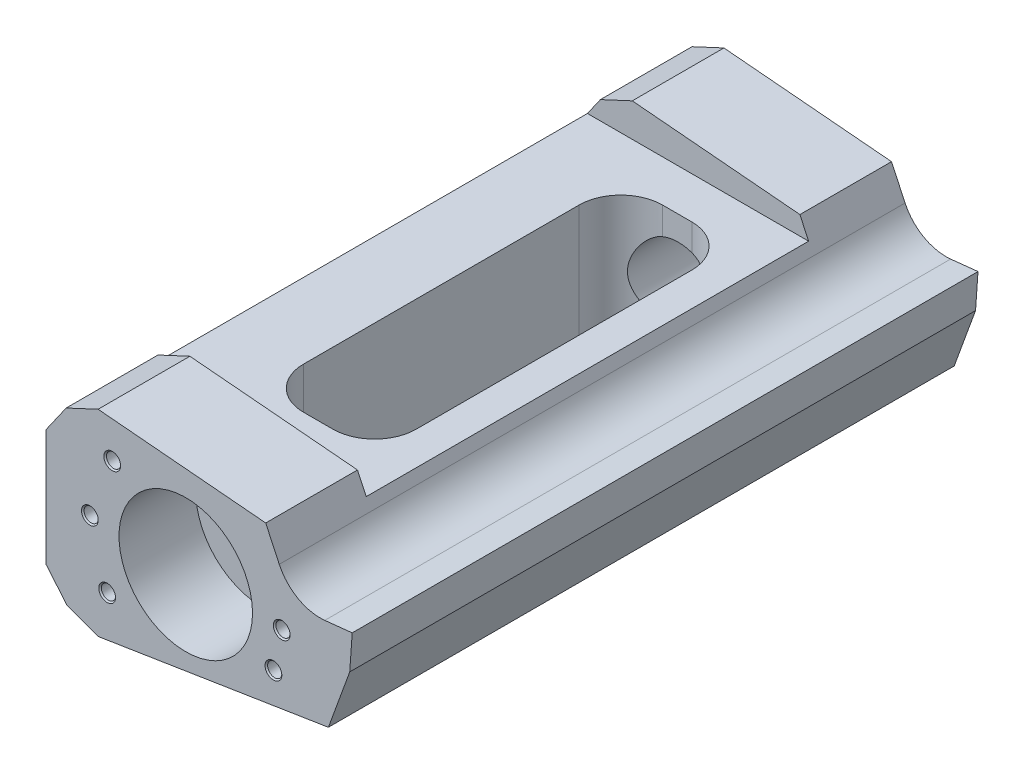
SolidWorks part; units mm, degrees
note: The reader was unsure of these and kept them because the rebuilt part matched: shared geometry of "Esboço7<3>".
material "AISI 4340 Aço, normalizado"
ref_plane "Plano frontal" through (0, 0, 0) normal (0, 0, 1) x (1, 0, 0)
ref_plane "Plano superior" through (0, 0, 0) normal (0, 1, 0) x (1, 0, 0)
ref_plane "Plano direito" through (0, 0, 0) normal (1, 0, 0) x (0, 0, -1)
other "Centro da massa"
sketch "Esboço1" plane through (0, 0, 0) normal (0, 0, 1) x (1, 0, 0)
  line L0 (0, 0) -> (23.1081, 0) construction
  line L1 (64.3164, 0) -> (63.3374, -14)
  line L2 (0, 0) -> (0, 38.7297) construction
  line L3 (-58, -37.4286) -> (54.8101, -37.4286)
  line L39 (29.7708, 20.7479) -> (-37.1899, 26.6062)
  line L40 (-37.1899, 26.6062) -> (-49.9344, 20.6633)
  line L41 (-49.9344, 20.6633) -> (-58, 9.1445)
  line L42 (-58, 9.1445) -> (-58, -37.4286)
  line L43 (-58, -37.4286) -> (-49.5472, -47.5023)
  line L44 (-49.5472, -47.5023) -> (-37.1899, -52)
  line L45 (-37.1899, -52) -> (54.8101, -37.4286)
  line L47 (54.8101, -37.4286) -> (63.3374, -14)
  line L49 (64.3164, 0) -> (53.3766, -1.1498)
  line L50 (35.1816, 9.1445) -> (29.7708, 20.7479)
  arc A0 (53.3766, -1.1498) -> (35.1816, 9.1445) centre (51.4951, 16.7516) cw
  dimension "D2" = 18
  dimension "D1" = 6
  dimension "D3" = 150
  dimension "D4" = 4
  dimension "D5" = 20
  dimension "D6" = 14
  dimension "D7" = 9
  dimension "D8" = 52
  dimension "D9" = 140
  dimension "D10" = 150
  dimension "D11" = 92
  dimension "D12" = 58
  dimension "D13" = 145
  dimension "D14" = 150
  dimension "D16" = 11
  dimension "D17" = 25
extrude "Ressalto-extrusão1" add sketch "Esboço1" along normal blind 250 contours L40 L41 L42 L43 L44 L45 L47 L1 L49 A0 L50 L39
scale "Escala1" scale about centroid uniform scaling yes scale factor 1.5
sketch "Esboço4" plane through (0, 0, -62.5) normal (0, 0, -1) x (-1, 0, 0)
  line L1 (-51.9784, 26.2892) -> (80.5703, 26.2892)
  line L3 (72.8079, 37.3749) -> (80.5703, 26.2892)
  line L4 (72.2271, -64.8736) -> (53.6913, -71.6201) construction
  line L5 (53.6913, -71.6201) -> (-84.3087, -49.763) construction
  line L9 (72.2271, -64.8736) -> (53.6913, -71.6201)
  line L10 (53.6913, -71.6201) -> (-84.3087, -49.763)
  line L11 (53.6913, 46.2892) -> (-46.7499, 37.5017)
  line L12 (-46.7499, 37.5017) -> (-54.866, 20.0966)
  line L13 (-82.1586, 4.6552) -> (-98.5682, 6.3799)
  line L14 (-98.5682, 6.3799) -> (-97.0997, -14.6201)
  line L15 (-97.0997, -14.6201) -> (-84.3087, -49.763)
  line L16 (-84.3087, -49.763) -> (53.6913, -71.6201)
  line L17 (53.6913, -71.6201) -> (72.2271, -64.8736)
  line L18 (72.2271, -64.8736) -> (84.9064, -49.763)
  line L19 (84.9064, -49.763) -> (84.9064, 20.0966)
  line L20 (84.9064, 20.0966) -> (72.8079, 37.3749)
  line L21 (72.8079, 37.3749) -> (53.6913, 46.2892)
  line L22 (53.6913, 46.2892) -> (-46.7499, 37.5017)
  line L32 (72.8079, 37.3749) -> (53.6913, 46.2892)
  line L38 (-54.866, 20.0966) -> (-46.7499, 37.5017) construction
  line L39 (72.8079, 37.3749) -> (84.9064, 20.0966) construction
  line L47 (-46.7499, 37.5017) -> (-51.9784, 26.2892)
  line L49 (84.9064, -49.763) -> (72.2271, -64.8736) construction
  line L50 (84.9064, -49.763) -> (72.2271, -64.8736)
  line L53 (-84.3087, -49.763) -> (84.9064, -49.763)
  line L54 (84.9064, 20.0966) -> (84.9064, -49.763) construction
  arc A1 (-82.1586, 4.6552) -> (-54.866, 20.0966) centre (-79.3363, 31.5073) ccw
  dimension "D2" = 20
  dimension "D1" = 0
extrude "Alívios superior / inferior" cut sketch "Esboço4" against normal offset from surface 55 and the other way blind 0.1 from offset 55 offset against normal yes
sketch "Esboço15" plane through (0, 26.2892, 0) normal (0, 1, 0) x (1, 0, 0)
  line L0 (-53.6913, 7.6) -> (46.7499, 7.6) construction
  line L1 (-10.5703, -17.4) -> (6.9784, -17.4)
  line L2 (-35.5703, -42.4) -> (-35.5703, -207.5)
  line L3 (-10.5703, -232.5) -> (6.9784, -232.5)
  line L4 (31.9784, -42.4) -> (31.9784, -207.5)
  line L5 (46.7499, -257.5) -> (-53.6913, -257.5) construction
  line L8 (-80.5703, 7.6) -> (-80.5703, -257.5) construction
  line L9 (51.9784, 7.6) -> (51.9784, -257.5) construction
  arc A0 (6.9784, -232.5) -> (31.9784, -207.5) centre (6.9784, -207.5) ccw
  arc A1 (-35.5703, -207.5) -> (-10.5703, -232.5) centre (-10.5703, -207.5) ccw
  arc A2 (6.9784, -17.4) -> (31.9784, -42.4) centre (6.9784, -42.4) cw
  arc A3 (-10.5703, -17.4) -> (-35.5703, -42.4) centre (-10.5703, -42.4) ccw
  dimension "D5" = 25
  dimension "D1" = 25
  dimension "D2" = 25
  dimension "D3" = 45
  dimension "D4" = 20
extrude "Alívio Central" cut sketch "Esboço15" against normal through all
sketch "Esboço7" plane through (0, 0, 312.5) normal (0, 0, 1) x (1, 0, 0)
  circle A0 centre (-1.1583, -13.2839) radius 40
  circle A1 centre (-1.1583, -13.2839) radius 25
  point P2 (-1.1583, -13.2839)
  dimension "D1" = 80
  dimension "D2" = 50
extrude "Rebaixo rolamento (Pai)" cut sketch "Esboço7" against normal blind 46 contours A0
extrude "Rebaixo rolamento (Filho)" cut sketch "Esboço7<3>" against normal through all contours A1
sketch "Esboço7<3>" plane through (0, 0, 312.5) normal (0, 0, 1) x (1, 0, 0) same geometry as "Esboço7"
extrude "Furo eixo arma (Filho)" cut sketch "Esboço7" along normal blind 46 from surface at -375 contours A0 starting at face at (23.8417, -13.2839, -62.5)
hole_wizard "Furos Polia (Pai)" positions "Esboço11" profile "Esboço12" tap size "M10" standard "ISO"
sketch "Esboço11" plane through (0, 0, 312.5) normal (0, 0, 1) x (1, 0, 0)
  line L0 (-1.1583, -13.2839) -> (-45.2059, 23.6764) construction
  line L1 (-1.1583, -13.2839) -> (-48.2595, -46.2646) construction
  line L2 (-1.1583, -13.2839) -> (51.3706, -36.6713) construction
  line L4 (-1.1583, -13.2839) -> (-58.6583, -13.2839) construction
  line L5 (-1.1583, -13.2839) -> (56.3417, -13.2839) construction
  circle A0 centre (-1.1583, -13.2839) radius 57.5
  circle A1 centre (-1.1583, -13.2839) radius 40 construction
  point P5 (-45.2059, 23.6764)
  point P7 (-58.6235, -11.2839)
  point P9 (-48.2595, -46.2646)
  point P11 (51.3706, -36.6713)
  point P13 (56.3417, -13.2839)
  dimension "D1" = 115
  dimension "D2" = 40
  dimension "D3" = 35
  dimension "D4" = 24
  dimension "D5" = 4
sketch "Esboço12" plane through (56.3417, -13.2839, 312.5) normal (1, 0, 0) x (0, -1, 0)
  line L0 (0, 0) -> (0, 30.0537)
  line L1 (0, 30.0537) -> (4.25, 27.5)
  line L2 (4.25, 27.5) -> (4.25, 0.775)
  line L3 (4.25, 0.775) -> (5.025, 0)
  line L5 (5.025, 0) -> (0, 0)
  line L6 (-4.25, 0.775) -> (-5.025, 0) construction
  line L10 (0, 30.0537) -> (-4.25, 27.5) construction
  line L11 (0, -6.35) -> (0, 107.95) construction
  dimension "Tap Drill Dia." = 8.5
  dimension "Tap Drill Depth" = 27.5
  dimension "Near C'Sink Dia." = 10.05
  dimension "Near C'Sink Angle" = 90
  dimension "Drill Angle" = 118
cosmetic thread "Rosca de furo8" parameters "D1"=20, "D2"=10
cosmetic thread "Rosca de furo9" parameters "D1"=20, "D2"=10
cosmetic thread "Rosca de furo10" parameters "D1"=20, "D2"=10
cosmetic thread "Rosca de furo16" parameters "D1"=20, "D2"=10
cosmetic thread "Rosca de furo17" parameters "D1"=20, "D2"=10
hole_wizard "Furos Polia (Filho)" positions "Esboço13" profile "Esboço14" tap size "M10" standard "ISO"
sketch "Esboço13" plane through (0, 0, -62.5) normal (0, 0, -1) x (-1, 0, 0)
  circle A0 centre (1.1583, -13.2839) radius 57.5 construction
  point P0 (45.2059, 23.6764)
  point P3 (58.6235, -11.2839)
  point P6 (48.2595, -46.2646)
  point P9 (-51.3706, -36.6713)
  point P13 (-56.3417, -13.2839)
sketch "Esboço14" plane through (-45.2059, 23.6764, -62.5) normal (1, 0, 0) x (0, 1, 0)
  line L0 (0, 0) -> (0, 30.0537)
  line L1 (0, 30.0537) -> (4.25, 27.5)
  line L2 (4.25, 27.5) -> (4.25, 0.775)
  line L3 (4.25, 0.775) -> (5.025, 0)
  line L5 (5.025, 0) -> (0, 0)
  line L6 (-4.25, 0.775) -> (-5.025, 0) construction
  line L10 (0, 30.0537) -> (-4.25, 27.5) construction
  line L11 (0, -6.35) -> (0, 107.95) construction
  dimension "Tap Drill Dia." = 8.5
  dimension "Tap Drill Depth" = 27.5
  dimension "Near C'Sink Dia." = 10.05
  dimension "Near C'Sink Angle" = 90
  dimension "Drill Angle" = 118
cosmetic thread "Rosca de furo13" parameters "D1"=20, "D2"=10
cosmetic thread "Rosca de furo14" parameters "D1"=20, "D2"=10
cosmetic thread "Rosca de furo15" parameters "D1"=20, "D2"=10
cosmetic thread "Rosca de furo18" parameters "D1"=20, "D2"=10
cosmetic thread "Rosca de furo19" parameters "D1"=20, "D2"=10
sketch "Esboço16" plane through (0, 0, 312.5) normal (0, 0, 1) x (1, 0, 0)
  circle A0 centre (-1.1583, -13.2839) radius 101.6466
  circle A1 centre (-1.1583, -13.2839) radius 40 construction
equation "\"rebaixo_rolamento_B\"=46"
equation "\"D1@Rebaixo rolamento (Pai)\"=\"rebaixo_rolamento_B\""
equation "\"D1@Furo eixo arma (Filho)\"=\"rebaixo_rolamento_B\""
